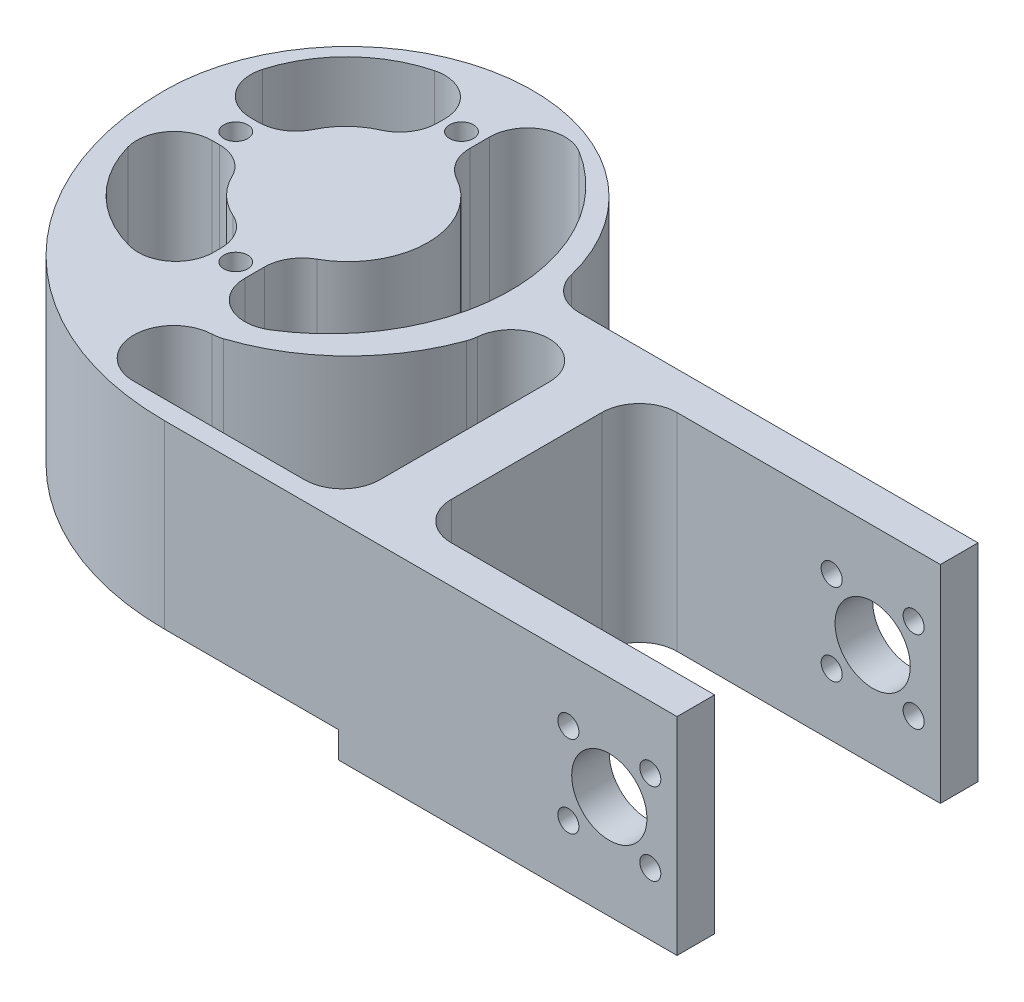
SolidWorks part; units mm, degrees
material "6061-T6 (SS)"
ref_plane "Front Plane" through (0, 0, 0) normal (0, 0, 1) x (1, 0, 0)
ref_plane "Top Plane" through (0, 0, 0) normal (0, 1, 0) x (1, 0, 0)
ref_plane "Right Plane" through (0, 0, 0) normal (1, 0, 0) x (0, 0, -1)
sketch "Sketch1" plane through (0, 0, 0) normal (0, 1, 0) x (1, 0, 0)
  circle A0 centre (0, 0) radius 31.0896
  dimension "D1" = 62.1792
extrude "Boss-Extrude1" add sketch "Sketch1" along normal blind 34.925
sketch "Sketch2" plane through (0, 34.925, 0) normal (0, 1, 0) x (1, 0, 0)
  line L0 (0, 0) -> (-31.0896, 0) construction
  line L1 (0, 0) -> (30.9857, 2.54) construction
  line L2 (46.5427, -48.26) -> (17.1704, -48.26)
  line L4 (46.5427, -48.26) -> (46.5427, 2.54)
  line L7 (30.9857, 2.54) -> (46.5427, 2.54)
  circle A0 centre (0, 0) radius 31.0896 construction
  arc A1 (17.1704, -48.26) -> (-31.0896, 0) centre (17.1704, 0) cw
  circle A2 centre (0, 0) radius 31.0896
  arc A3 (-31.0896, 0) -> (30.9857, 2.54) centre (0, 0) ccw
  dimension "D3" = 2.54
  dimension "D1" = 50.8
  dimension "D2" = 15.557
  dimension "D4" = 0
extrude "Boss-Extrude2" add sketch "Sketch2" against normal blind 30.48
sketch "Sketch3" plane through (0, 34.925, 0) normal (0, 1, 0) x (1, 0, 0)
  line L0 (46.5427, -0.3336) -> (46.5427, -48.26)
  line L1 (17.1704, -48.26) -> (46.5427, -48.26) construction
  line L2 (46.5427, -48.26) -> (103.6927, -48.26)
  line L3 (103.6927, -48.26) -> (103.6927, -41.91)
  line L4 (103.6927, -41.91) -> (52.8927, -41.91)
  line L5 (52.8927, -41.91) -> (52.8927, -3.81)
  line L6 (52.8927, -3.81) -> (103.6927, -3.81)
  line L7 (103.6927, -3.81) -> (103.6927, 2.54)
  line L8 (103.6927, 2.54) -> (46.5427, 2.54)
  line L9 (46.5427, -0.3336) -> (46.5427, 2.54)
  line L10 (46.5427, -48.26) -> (46.5427, 2.54) construction
  dimension "D1" = 57.15
  dimension "D2" = 38.1
  dimension "D3" = 6.35
  dimension "D4" = 6.35
extrude "Boss-Extrude3" add sketch "Sketch3" against normal up to surface (34.925 mm away) up to face at (0, 0, 31.0896)
sketch "Sketch4" plane through (0, 0, -2.54) normal (0, 0, -1) x (-1, 0, 0)
  line L0 (-103.6927, 17.4625) -> (-92.2627, 17.4625) construction
  line L1 (-103.6927, 0) -> (-103.6927, 34.925) construction
  line L2 (-92.2627, 17.4625) -> (-99.1775, 10.5477) construction
  line L3 (-92.2627, 17.4625) -> (-99.1775, 24.3773) construction
  line L4 (-92.2627, 17.4625) -> (-99.1775, 10.5477) construction
  line L5 (-92.2627, 17.4625) -> (-85.3479, 10.5477) construction
  line L6 (-92.2627, 17.4625) -> (-85.3479, 24.3773) construction
  line L8 (-99.1775, 24.3773) -> (-103.6927, 24.3773) construction
  line L9 (-103.6927, 0) -> (-103.6927, 34.925) construction
  line L10 (-99.1775, 10.5477) -> (-103.6927, 10.5477) construction
  circle A0 centre (-92.2627, 17.4625) radius 6.35
  circle A1 centre (-85.3479, 10.5477) radius 1.778
  circle A3 centre (-99.1775, 24.3773) radius 1.778
  circle A4 centre (-99.1775, 10.5477) radius 1.778
  circle A5 centre (-85.3479, 24.3773) radius 1.778
  dimension "D1" = 11.43
  dimension "D2" = 12.7
  dimension "D3" = 3.556
  dimension "D5" = 19.558
  dimension "D4" = 19.558
extrude "Cut-Extrude1" cut sketch "Sketch4" against normal up to surface (50.8 mm away) up to face at (53.3542, 12.7529, 48.26)
sketch "Sketch5" plane through (0, 34.925, 0) normal (0, 1, 0) x (1, 0, 0)
  line L0 (0, 0) -> (-9.2497, 9.2497) construction
  line L1 (0, 0) -> (9.2497, -9.2497) construction
  line L2 (0, 0) -> (-9.2497, -9.2497) construction
  line L3 (0, 0) -> (9.2497, 9.2497) construction
  line L4 (-9.2497, -9.2497) -> (9.2497, -9.2497)
  line L5 (9.2497, -9.2497) -> (9.2497, 9.2497)
  line L6 (9.2497, 9.2497) -> (-9.2497, 9.2497)
  line L7 (-9.2497, 9.2497) -> (-9.2497, -9.2497)
  point P0 (0, 0)
  dimension "D1" = 26.162
extrude "Cut-Extrude2" cut sketch "Sketch5" along normal blind 12.7 from surface starting at face at (0, 0, 31.0896)
fillet "Fillet8" radius 6.35 1 edges at (30.9857, 19.685, -2.54)
fillet "Fillet16" radius 2.54 1 edges at (-9.2497, 6.35, -9.2497)
fillet "Fillet18" radius 2.54 1 edges at (-9.2497, 6.35, 9.2497)
fillet "Fillet17" radius 2.54 1 edges at (9.2497, 6.35, 9.2497)
fillet "Fillet15" radius 2.54 1 edges at (9.2497, 6.35, -9.2497)
fillet "Fillet9" radius 6.35 1 edges at (52.8927, 17.4625, 41.91)
fillet "Fillet10" radius 6.35 1 edges at (52.8927, 17.4625, 3.81)
sketch "Sketch6" plane through (0, 34.925, 0) normal (0, 1, 0) x (1, 0, 0)
  line L4 (103.6927, 2.54) -> (36.3688, 2.54)
  line L5 (103.6927, 2.54) -> (36.3688, 2.54)
  line L6 (17.1704, -48.26) -> (103.6927, -48.26)
  line L7 (17.1704, -48.26) -> (103.6927, -48.26)
  line L8 (103.6927, -48.26) -> (103.6927, -41.91)
  line L9 (103.6927, -48.26) -> (103.6927, -41.91)
  line L10 (103.6927, -41.91) -> (59.2427, -41.91)
  line L11 (103.6927, -41.91) -> (59.2427, -41.91)
  line L12 (59.2427, -0.635) -> (36.3688, -0.635)
  line L13 (59.2427, -0.635) -> (36.3688, -0.635)
  line L14 (17.1704, -45.085) -> (59.2427, -45.085)
  line L15 (17.1704, -45.085) -> (59.2427, -45.085)
  line L16 (49.7177, -35.56) -> (49.7177, -10.16)
  line L17 (49.7177, -35.56) -> (49.7177, -10.16)
  line L23 (52.8927, -35.56) -> (52.8927, -10.16)
  line L24 (52.8927, -35.56) -> (52.8927, -10.16)
  line L25 (59.2427, -3.81) -> (103.6927, -3.81)
  line L26 (59.2427, -3.81) -> (103.6927, -3.81)
  line L27 (103.6927, -3.81) -> (103.6927, 2.54)
  line L28 (103.6927, -3.81) -> (103.6927, 2.54)
  arc A5 (30.2004, 7.3822) -> (36.3688, 2.54) centre (36.3688, 8.89) ccw
  arc A6 (30.2004, 7.3822) -> (36.3688, 2.54) centre (36.3688, 8.89) ccw
  arc A7 (30.2004, 7.3822) -> (-31.0896, 0) centre (0, 0) ccw
  arc A8 (30.2004, 7.3822) -> (-31.0896, 0) centre (0, 0) ccw
  arc A9 (-31.0896, 0) -> (17.1704, -48.26) centre (17.1704, 0) ccw
  arc A10 (-31.0896, 0) -> (17.1704, -48.26) centre (17.1704, 0) ccw
  arc A11 (52.8927, -35.56) -> (59.2427, -41.91) centre (59.2427, -35.56) ccw
  arc A12 (52.8927, -35.56) -> (59.2427, -41.91) centre (59.2427, -35.56) ccw
  arc A13 (59.2427, -3.81) -> (52.8927, -10.16) centre (59.2427, -10.16) ccw
  arc A14 (59.2427, -3.81) -> (52.8927, -10.16) centre (59.2427, -10.16) ccw
  arc A15 (27.1162, 6.6283) -> (36.3688, -0.635) centre (36.3688, 8.89) ccw
  arc A16 (27.1162, 6.6283) -> (36.3688, -0.635) centre (36.3688, 8.89) ccw
  arc A17 (27.1162, 6.6283) -> (-27.9146, 0) centre (0, 0) ccw
  arc A18 (27.1162, 6.6283) -> (-27.9146, 0) centre (0, 0) ccw
  arc A19 (-27.9146, 0) -> (17.1704, -45.085) centre (17.1704, 0) ccw
  arc A20 (43.6884, -0.635) -> (49.9101, -8.255) centre (43.6884, -6.985) cw
  arc A21 (43.6884, -45.085) -> (49.9101, -37.465) centre (43.6884, -38.735) ccw
  arc A22 (-27.9146, 0) -> (17.1704, -45.085) centre (17.1704, 0) ccw
  arc A23 (49.7177, -35.56) -> (59.2427, -45.085) centre (59.2427, -35.56) ccw
  arc A24 (49.7177, -35.56) -> (59.2427, -45.085) centre (59.2427, -35.56) ccw
  arc A25 (59.2427, -0.635) -> (49.7177, -10.16) centre (59.2427, -10.16) ccw
  arc A26 (59.2427, -0.635) -> (49.7177, -10.16) centre (59.2427, -10.16) ccw
  dimension "D3" = 6.35
  dimension "D1" = 0
  dimension "D2" = 3.175
extrude "Cut-Extrude3" [suppressed] cut sketch "Sketch6" against normal blind 19.05
sketch "Sketch8" [suppressed] plane through (0, 15.875, 0) normal (0, 1, 0) x (1, 0, 0)
  line L1 (35.1127, -2.54) -> (41.4627, -2.54)
  line L2 (28.7627, -8.89) -> (28.7627, -36.83)
  line L3 (47.8127, -8.89) -> (47.8127, -36.83)
  line L6 (35.1127, -43.18) -> (41.4627, -43.18)
  line L7 (103.6927, 2.54) -> (36.3688, 2.54) construction
  line L8 (52.8927, -35.56) -> (52.8927, -10.16) construction
  line L9 (17.1704, -48.26) -> (103.6927, -48.26) construction
  arc A0 (28.7627, -36.83) -> (35.1127, -43.18) centre (35.1127, -36.83) ccw
  arc A1 (47.8127, -36.83) -> (41.4627, -43.18) centre (41.4627, -36.83) cw
  arc A2 (41.4627, -2.54) -> (47.8127, -8.89) centre (41.4627, -8.89) cw
  arc A3 (28.7627, -8.89) -> (35.1127, -2.54) centre (35.1127, -8.89) cw
  dimension "D1" = 6.35
  dimension "D2" = 5.08
  dimension "D3" = 5.08
  dimension "D4" = 19.05
  dimension "D5" = 5.08
extrude "Cut-Extrude4" [suppressed] cut sketch "Sketch8" against normal up to surface (11.43 mm away) up to face at (21.5778, 4.445, 25.8461)
sketch "Sketch9" [suppressed] plane through (0, 15.875, 0) normal (0, 1, 0) x (1, 0, 0)
  line L0 (-9.3373, 19.4097) -> (-9.3373, 18.7747)
  line L1 (-2.9873, 12.4247) -> (3.3627, 12.4247)
  line L2 (9.7127, 18.7747) -> (9.7127, 19.4097)
  line L3 (-2.9873, 25.7597) -> (3.3627, 25.7597)
  line L4 (-6.7097, 9.2497) -> (6.7097, 9.2497) construction
  line L5 (28.7627, -11.8013) -> (28.7627, -8.89) construction
  line L6 (-9.2497, -6.7097) -> (-9.2497, 6.7097) construction
  line L7 (9.2497, 6.7097) -> (9.2497, -6.7097) construction
  line L9 (-9.2497, 0) -> (9.2497, 0) construction
  line L10 (9.7127, -18.7747) -> (9.7127, -19.4097)
  line L11 (-2.9873, -12.4247) -> (3.3627, -12.4247)
  line L12 (-9.3373, -19.4097) -> (-9.3373, -18.7747)
  line L13 (-2.9873, -25.7597) -> (3.3627, -25.7597)
  arc A0 (3.3627, 12.4247) -> (9.7127, 18.7747) centre (3.3627, 18.7747) ccw
  arc A1 (-9.3373, 18.7747) -> (-2.9873, 12.4247) centre (-2.9873, 18.7747) ccw
  arc A2 (-9.3373, 19.4097) -> (-2.9873, 25.7597) centre (-2.9873, 19.4097) cw
  arc A3 (9.7127, 19.4097) -> (3.3627, 25.7597) centre (3.3627, 19.4097) ccw
  arc A4 (3.3627, -12.4247) -> (9.7127, -18.7747) centre (3.3627, -18.7747) cw
  arc A5 (-9.3373, -18.7747) -> (-2.9873, -12.4247) centre (-2.9873, -18.7747) cw
  arc A6 (-9.3373, -19.4097) -> (-2.9873, -25.7597) centre (-2.9873, -19.4097) ccw
  arc A7 (9.7127, -19.4097) -> (3.3627, -25.7597) centre (3.3627, -19.4097) cw
  dimension "D1" = 6.35
  dimension "D2" = 3.175
  dimension "D3" = 16.51
  dimension "D4" = 19.05
  dimension "D5" = 19.05
extrude "Cut-Extrude5" [suppressed] cut sketch "Sketch9" against normal up to surface (11.43 mm away) up to face at (21.5778, 4.445, 25.8461)
sketch "Sketch11" plane through (0, 4.445, 0) normal (0, -1, 0) x (-1, 0, 0)
  line L0 (-44.0027, -10.16) -> (-44.0027, -38.735)
  line L1 (-8.4427, -45.085) -> (-37.6527, -45.085)
  line L2 (-8.4427, -45.085) -> (-8.8214, -38.3416) construction
  line L3 (-8.8214, -38.3416) -> (-9.2001, -31.5981) construction
  line L5 (-17.1704, -48.26) -> (-46.5427, -48.26) construction
  line L6 (-46.5427, -48.26) -> (-46.5427, 2.54) construction
  line L7 (-31.3027, -10.16) -> (-44.0027, -10.16) construction
  arc A0 (-44.0027, -10.16) -> (-31.3322, -9.5481) centre (-37.6527, -10.16) cw
  arc A1 (-44.0027, -38.735) -> (-37.6527, -45.085) centre (-37.6527, -38.735) ccw
  arc A2 (-8.5205, -31.5942) -> (-8.4427, -45.085) centre (-8.8214, -38.3416) cw
  arc A3 (-10.207, -31.2874) -> (-8.5205, -31.5942) centre (-8.2376, -25.2505) ccw
  arc A4 (-30.9916, -11.0728) -> (-10.207, -31.2874) centre (0, 0) ccw
  arc A5 (-31.3322, -9.5481) -> (-30.9916, -11.0728) centre (-25.0118, -8.9363) ccw
  dimension "D1" = 12.7
  dimension "D3" = 3.175
  dimension "D2" = 6.35
  dimension "D5" = 6.7541
  dimension "D7" = 6.35
  dimension "D8" = 6.35
  dimension "D4" = 28.575
  dimension "D6" = 29.21
  dimension "D10" = 2.54
  dimension "D11" = 38.1
extrude "Cut-Extrude6" cut sketch "Sketch11" against normal up to surface (30.48 mm away) up to face at (56.2464, 34.925, 17.0919)
sketch "Sketch12" plane through (0, 0, 0) normal (0, -1, 0) x (1, 0, 0)
  line L0 (0, 0) -> (0, -19.05) construction
  line L1 (0, 0) -> (0, 19.05) construction
  line L2 (0, 0) -> (-19.05, 0) construction
  line L3 (0, 0) -> (19.05, 0) construction
  circle A0 centre (0, 19.05) radius 2.0193
  circle A1 centre (-19.05, 0) radius 2.0193
  circle A2 centre (0, -19.05) radius 2.0193
  dimension "D1" = 4.0386
  dimension "D2" = 19.05
extrude "Cut-Extrude7" cut sketch "Sketch12" against normal up to surface (34.925 mm away) up to face at (26.5935, 34.925, 27.5361)
sketch "Sketch13" plane through (0, 0, 0) normal (0, -1, 0) x (1, 0, 0)
  line L0 (3.1444, -17.348) -> (3.1444, -20.6681)
  line L1 (3.1444, 20.6681) -> (3.1444, 17.348)
  line L2 (13.3802, 0) -> (9.2497, 0) construction
  line L3 (-0.0887, 0) -> (-20.4631, -20.4868) construction
  line L4 (13.3802, 0) -> (27.3502, 0) construction
  line L5 (0, 19.05) -> (3.1444, 19.05) construction
  line L6 (0, -19.05) -> (3.1444, -19.05) construction
  line L7 (-3.2838, -18.2655) -> (-3.2838, -19.5355)
  line L8 (-19.7907, -3.2865) -> (-18.5207, -3.2865)
  line L9 (-10.4219, -10.1865) -> (-0.0887, 0) construction
  line L11 (-18.5207, -3.2865) -> (-9.3147, -3.2865) construction
  line L12 (-19.1557, -2.0165) -> (-9.2497, -2.0165) construction
  line L13 (-3.2838, -18.2655) -> (-3.2838, -9.0595) construction
  line L15 (-19.1557, -3.2865) -> (-19.1557, -2.0165) construction
  line L16 (-3.2838, -18.9005) -> (-2.0138, -18.9005) construction
  line L17 (0, 0) -> (-31.0896, 0) construction
  line L18 (-3.2838, 18.2655) -> (-3.2838, 19.5355)
  line L19 (-19.7907, 3.2865) -> (-18.5207, 3.2865)
  line L20 (8.8973, -10.0331) -> (8.5057, -8.5057) construction
  line L21 (8.8973, 10.0331) -> (8.5057, 8.5057) construction
  line L22 (9.2497, -6.7097) -> (9.2497, 6.7097) construction
  line L23 (-9.2497, 6.7097) -> (-9.2497, -6.7097) construction
  line L25 (6.424, -11.7897) -> (6.424, -9.2497) construction
  line L26 (-6.7097, -9.2497) -> (6.7097, -9.2497) construction
  arc A0 (12.8397, 26.0654) -> (12.8397, -26.0654) centre (-3.316, 0) cw
  arc A1 (6.424, -11.7897) -> (6.424, 11.7897) centre (-0.0887, 0) ccw
  arc A2 (3.1444, 20.6681) -> (12.8397, 26.0654) centre (9.4944, 20.6681) cw
  arc A3 (3.1444, 17.348) -> (6.424, 11.7897) centre (9.4944, 17.348) ccw
  arc A4 (12.8397, -26.0654) -> (3.1444, -20.6681) centre (9.4944, -20.6681) cw
  arc A5 (3.1444, -17.348) -> (6.424, -11.7897) centre (9.4944, -17.348) cw
  arc A6 (-12.7964, -6.8877) -> (-7.0547, -12.4629) centre (-2.3464, -1.8696) ccw
  arc A7 (-11.2152, -25.6854) -> (-25.8979, -11.3756) centre (-6.0845, -5.7336) cw
  arc A8 (-18.5207, -3.2865) -> (-12.7964, -6.8877) centre (-18.5207, -9.6365) cw
  arc A9 (-3.2838, -19.5355) -> (-11.2152, -25.6854) centre (-9.6338, -19.5355) cw
  arc A10 (-3.2838, -18.2655) -> (-7.0547, -12.4629) centre (-9.6338, -18.2655) ccw
  arc A11 (-19.7907, -3.2865) -> (-25.8979, -11.3756) centre (-19.7907, -9.6365) ccw
  circle A12 centre (-19.05, 0) radius 2.0193 construction
  circle A13 centre (0, -19.05) radius 2.0193 construction
  arc A14 (-11.2152, 25.6854) -> (-25.8979, 11.3756) centre (-6.0845, 5.7336) ccw
  arc A15 (-3.2838, 19.5355) -> (-11.2152, 25.6854) centre (-9.6338, 19.5355) ccw
  arc A16 (-3.2838, 18.2655) -> (-7.0547, 12.4629) centre (-9.6338, 18.2655) cw
  arc A17 (-12.7964, 6.8877) -> (-7.0547, 12.4629) centre (-2.3464, 1.8696) cw
  arc A18 (-18.5207, 3.2865) -> (-12.7964, 6.8877) centre (-18.5207, 9.6365) ccw
  arc A19 (-19.7907, 3.2865) -> (-25.8979, 11.3756) centre (-19.7907, 9.6365) cw
  arc A23 (6.7097, -9.2497) -> (9.2497, -6.7097) centre (6.7097, -6.7097) ccw construction
  arc A24 (9.2497, 6.7097) -> (6.7097, 9.2497) centre (6.7097, 6.7097) ccw construction
  dimension "D1" = 6.35
  dimension "D2" = 6.35
  dimension "D3" = 6.35
  dimension "D8" = 1.5768
  dimension "D9" = 6.35
  dimension "D10" = 6.35
  dimension "D4" = 3.3201
  dimension "D5" = 4.1305
  dimension "D6" = 13.97
  dimension "D7" = 3.1444
  dimension "D11" = 1.27
  dimension "D12" = 9.206
  dimension "D13" = 2.54
  dimension "D14" = 28.8933
  dimension "D15" = 14.51
  dimension "D16" = 1.27
  dimension "D17" = 14.2775
  dimension "D18" = 9.906
extrude "Cut-Extrude8" cut sketch "Sketch13" against normal up to surface (34.925 mm away) up to face at (0, 34.925, -17.0307)
